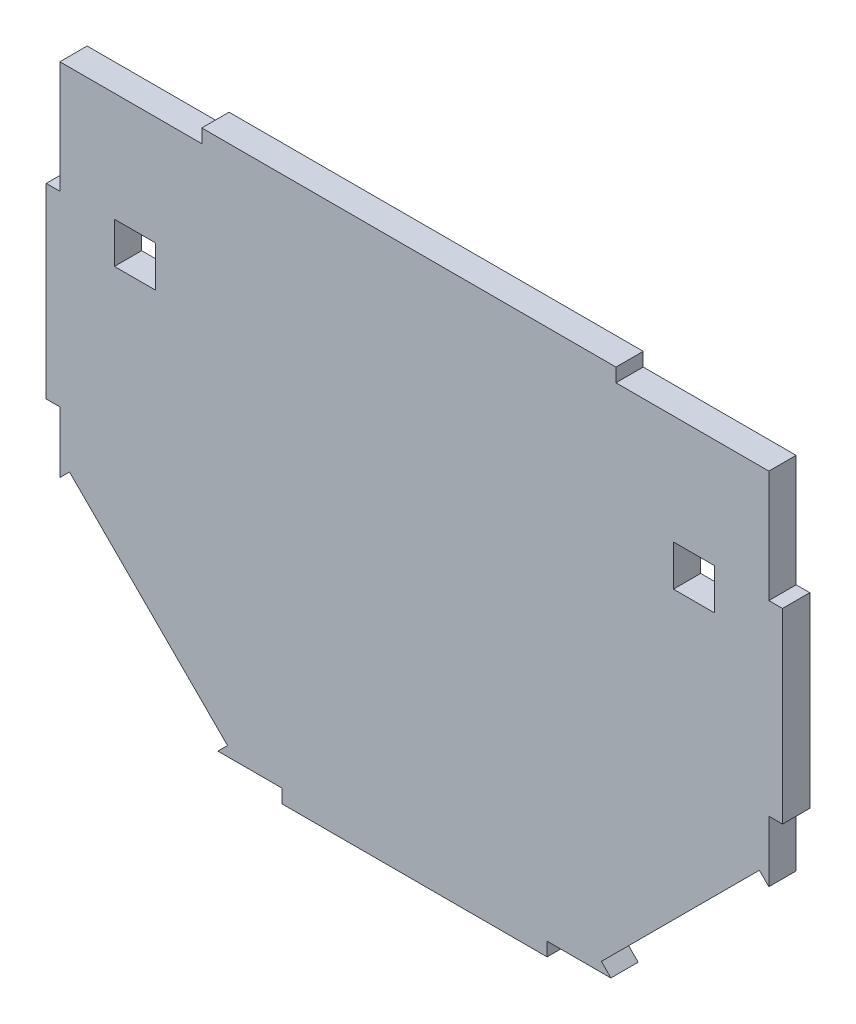
SolidWorks part; units mm, degrees
ref_plane "Front Plane" through (0, 0, 0) normal (0, 0, 1) x (1, 0, 0)
ref_plane "Top Plane" through (0, 0, 0) normal (0, 1, 0) x (1, 0, 0)
ref_plane "Right Plane" through (0, 0, 0) normal (1, 0, 0) x (0, 0, -1)
sketch "Sketch1" plane through (0, 0, 0) normal (0, 0, 1) x (1, 0, 0)
  line L0 (412.0154, 1072.6191) -> (767.6154, 1072.6191) construction
  line L1 (767.6154, 1072.6191) -> (767.6154, 886.9451) construction
  line L2 (767.6154, 886.9451) -> (686.5894, 805.9673) construction
  line L3 (686.5894, 805.9673) -> (493.0414, 805.9673) construction
  line L4 (493.0414, 805.9673) -> (412.0154, 886.9451) construction
  line L5 (412.0154, 886.9451) -> (412.0154, 1072.6191) construction
  line L6 (424.7154, 892.2078) -> (424.7154, 920.7157)
  line L7 (424.7154, 1059.9191) -> (490.8067, 1059.9191)
  line L8 (754.9154, 1059.9191) -> (754.9154, 1007.6919)
  line L9 (754.9154, 892.2078) -> (681.3311, 818.6673)
  line L10 (681.3311, 818.6673) -> (651.6344, 818.6673)
  line L11 (498.2997, 818.6673) -> (424.7154, 892.2078)
  line L21 (424.7154, 1007.6919) -> (424.7154, 1059.9191)
  line L22 (424.7154, 892.2078) -> (424.7154, 1059.9191) construction
  line L23 (754.9154, 920.7157) -> (754.9154, 892.2078)
  line L24 (754.9154, 1059.9191) -> (754.9154, 892.2078) construction
  line L25 (528.0648, 818.6673) -> (498.2997, 818.6673)
  line L26 (681.3311, 818.6673) -> (498.2997, 818.6673) construction
  line L30 (683.7, 1059.9191) -> (754.9154, 1059.9191)
  line L31 (424.7154, 1059.9191) -> (754.9154, 1059.9191) construction
  line L32 (424.7154, 920.7157) -> (418.3654, 920.7157)
  line L33 (418.3654, 920.7157) -> (418.3654, 1007.6919)
  line L34 (418.3654, 1007.6919) -> (424.7154, 1007.6919)
  line L35 (490.8067, 1059.9191) -> (490.8067, 1066.2691)
  line L38 (754.9154, 1007.6919) -> (761.2654, 1007.6919)
  line L39 (761.2654, 1007.6919) -> (761.2654, 920.7157)
  line L40 (761.2654, 920.7157) -> (754.9154, 920.7157)
  line L41 (651.6344, 818.6673) -> (651.6344, 812.3173)
  line L42 (651.6344, 812.3173) -> (528.0648, 812.3173)
  line L43 (528.0648, 812.3173) -> (528.0648, 818.6673)
  line L44 (683.7, 1059.9191) -> (683.7, 1066.2691)
  line L45 (683.7, 1066.2691) -> (490.8067, 1066.2691)
  dimension "D1" = 355.6
  dimension "D2" = 185.674
  dimension "D3" = 114.554
  dimension "D4" = 193.548
  dimension "D6" = 6.35
  dimension "D7" = 6.35
  dimension "D8" = 6.35
  dimension "D9" = 6.35
  dimension "D5" = 12.7
extrude "Boss-Extrude1" add sketch "Sketch1" along normal blind 12.7
sketch "Sketch2" plane through (0, 0, 12.7) normal (0, 0, 1) x (1, 0, 0)
  line L0 (424.7154, 1059.9191) -> (424.7154, 1007.6919) construction
  line L5 (450.1154, 1009.1191) -> (469.1654, 1009.1191)
  line L6 (450.1154, 1009.1191) -> (450.1154, 990.0691)
  line L7 (450.1154, 990.0691) -> (469.1654, 990.0691)
  line L8 (469.1654, 1009.1191) -> (469.1654, 990.0691)
  line L9 (710.4654, 1009.1191) -> (729.5154, 1009.1191)
  line L10 (710.4654, 1009.1191) -> (710.4654, 990.0691)
  line L11 (710.4654, 990.0691) -> (729.5154, 990.0691)
  line L12 (729.5154, 1009.1191) -> (729.5154, 990.0691)
  line L13 (490.8067, 1059.9191) -> (424.7154, 1059.9191) construction
  line L14 (754.9154, 1007.6919) -> (754.9154, 1059.9191) construction
  line L15 (754.9154, 1059.9191) -> (683.7, 1059.9191) construction
  dimension "D1" = 25.4
  dimension "D2" = 50.8
  dimension "D3" = 25.4
  dimension "D4" = 50.8
  dimension "D5" = 19.05
extrude "Cut-Extrude1" cut sketch "Sketch2" against normal through all
sketch "Sketch3" plane through (0, 0, 12.7) normal (0, 0, 1) x (1, 0, 0)
  line L0 (589.8496, 812.3173) -> (589.8496, 1066.2691) construction
  line L1 (528.0648, 812.3173) -> (651.6344, 812.3173) construction
  line L2 (683.7, 1066.2691) -> (490.8067, 1066.2691) construction
  line L3 (424.7154, 892.2078) -> (498.2997, 818.6673) construction
  line L4 (429.2042, 896.6993) -> (502.7885, 823.1588)
  line L5 (429.2042, 896.6993) -> (424.7154, 892.2078)
  line L6 (502.7885, 823.1588) -> (498.2997, 818.6673)
  line L7 (750.495, 896.6993) -> (754.9838, 892.2078)
  line L8 (676.9107, 823.1588) -> (681.3995, 818.6673)
  line L9 (750.495, 896.6993) -> (676.9107, 823.1588)
  line L10 (424.7154, 892.2078) -> (498.2997, 818.6673)
  line L11 (754.9838, 892.2078) -> (681.3995, 818.6673)
  dimension "D1" = 6.35
extrude "Cut-Extrude2" cut sketch "Sketch3" against normal through all
